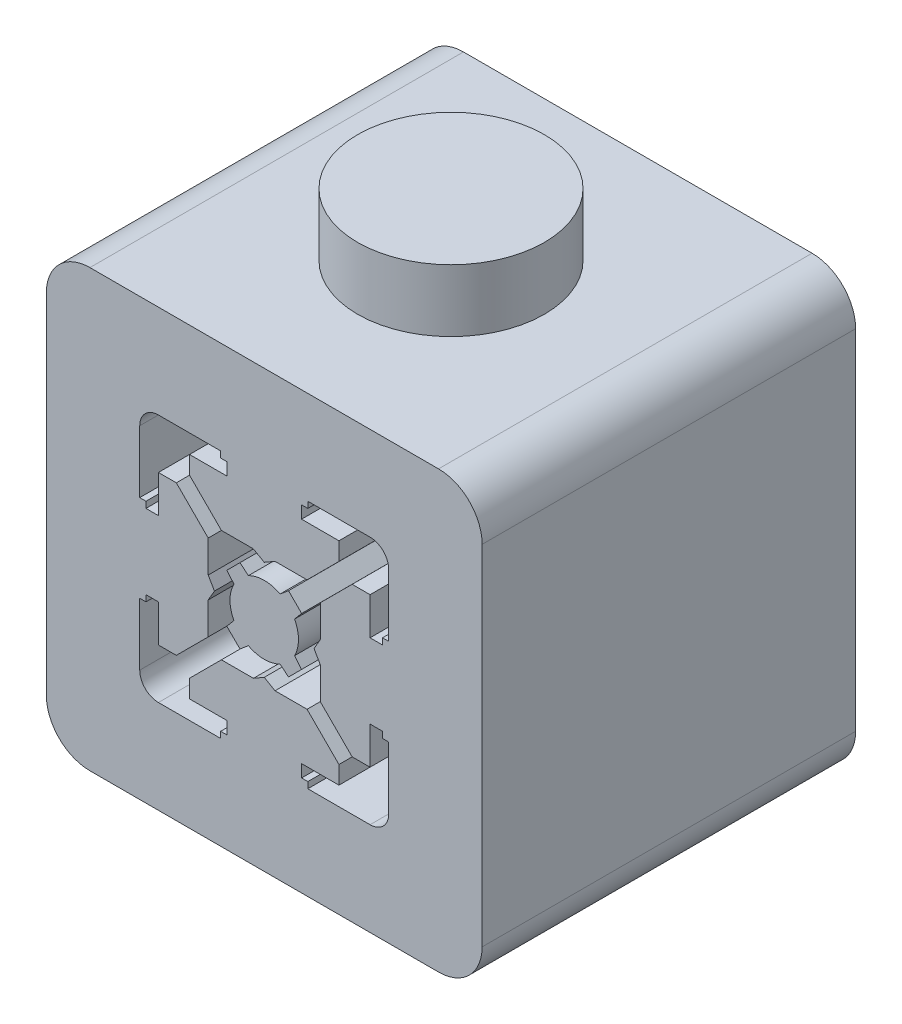
SolidWorks part; units mm, degrees
ref_plane "Plan de face" through (0, 0, 0) normal (0, 0, 1) x (1, 0, 0)
ref_plane "Plan de dessus" through (0, 0, 0) normal (0, 1, 0) x (1, 0, 0)
ref_plane "Plan de droite" through (0, 0, 0) normal (1, 0, 0) x (0, 0, -1)
sketch "Esquisse1" plane through (0, 0, 0) normal (0, 0, 1) x (1, 0, 0)
  line L0 (0, 0) -> (-4, 0) construction
  line L1 (-4, 0) -> (-4.5, 0.866)
  line L2 (-4, 0) -> (-4.5, -0.866)
  line L15 (-4.5, 0.866) -> (-4.5, 3.4393)
  line L16 (-4.5, 3.4393) -> (-7.0607, 6)
  line L17 (-7.0607, 6) -> (-8.5, 6)
  line L18 (-8.5, 6) -> (-8.5, 3)
  line L19 (-8.5, 3) -> (-9.5, 3)
  line L20 (-9.5, 3) -> (-9.5, 3.5)
  line L21 (-9.5, 3.5) -> (-10, 3.5)
  line L22 (-10, 3.5) -> (-10, 8.5)
  line L23 (0, 0) -> (0, 1.2745) construction
  line L24 (10, -3.5) -> (10, -8.5)
  line L25 (4.5, -3.4393) -> (7.0607, -6)
  line L26 (-9.5, -3.5) -> (-10, -3.5)
  line L27 (-9.5, -3) -> (-9.5, -3.5)
  line L28 (-8.5, -3) -> (-9.5, -3)
  line L29 (-8.5, -6) -> (-8.5, -3)
  line L30 (-7.0607, -6) -> (-8.5, -6)
  line L31 (-4.5, -0.866) -> (-4.5, -3.4393)
  line L32 (-4.5, -3.4393) -> (-7.0607, -6)
  line L33 (-10, -3.5) -> (-10, -8.5)
  line L34 (4.5, -0.866) -> (4.5, -3.4393)
  line L35 (7.0607, -6) -> (8.5, -6)
  line L36 (8.5, -6) -> (8.5, -3)
  line L37 (8.5, -3) -> (9.5, -3)
  line L38 (9.5, -3) -> (9.5, -3.5)
  line L39 (9.5, -3.5) -> (10, -3.5)
  line L40 (10, 3.5) -> (10, 8.5)
  line L41 (9.5, 3.5) -> (10, 3.5)
  line L42 (9.5, 3) -> (9.5, 3.5)
  line L43 (8.5, 3) -> (9.5, 3)
  line L44 (8.5, 6) -> (8.5, 3)
  line L45 (7.0607, 6) -> (8.5, 6)
  line L46 (4.5, 3.4393) -> (7.0607, 6)
  line L47 (4.5, 0.866) -> (4.5, 3.4393)
  line L48 (4, 0) -> (4.5, -0.866)
  line L49 (4, 0) -> (4.5, 0.866)
  line L50 (3.5, 10) -> (8.5, 10)
  line L51 (3.5, 9.5) -> (3.5, 10)
  line L52 (3, 8.5) -> (3, 9.5)
  line L53 (3, 9.5) -> (3.5, 9.5)
  line L54 (6, 8.5) -> (3, 8.5)
  line L55 (6, 7.0607) -> (6, 8.5)
  line L56 (3.4393, 4.5) -> (6, 7.0607)
  line L57 (0.866, 4.5) -> (3.4393, 4.5)
  line L58 (-0.866, 4.5) -> (-3.4393, 4.5)
  line L59 (-3.4393, 4.5) -> (-6, 7.0607)
  line L60 (-6, 7.0607) -> (-6, 8.5)
  line L61 (-6, 8.5) -> (-3, 8.5)
  line L62 (-3, 8.5) -> (-3, 9.5)
  line L63 (-3, 9.5) -> (-3.5, 9.5)
  line L64 (-3.5, 9.5) -> (-3.5, 10)
  line L65 (-3.5, 10) -> (-8.5, 10)
  line L66 (-14, 17.5) -> (14, 17.5)
  line L67 (9.5, -3.5) -> (10, -3.5)
  line L68 (8.5, -3) -> (9.5, -3)
  line L69 (9.5, -3) -> (9.5, -3.5)
  line L70 (8.5, -6) -> (8.5, -3)
  line L71 (7.0607, -6) -> (8.5, -6)
  line L72 (4.5, -3.4393) -> (7.0607, -6)
  line L73 (4.5, -0.866) -> (4.5, -3.4393)
  line L74 (4.5, 0.866) -> (4.5, 3.4393)
  line L75 (4.5, 3.4393) -> (7.0607, 6)
  line L76 (7.0607, 6) -> (8.5, 6)
  line L77 (8.5, 6) -> (8.5, 3)
  line L78 (8.5, 3) -> (9.5, 3)
  line L79 (9.5, 3) -> (9.5, 3.5)
  line L80 (9.5, 3.5) -> (10, 3.5)
  line L82 (-3.5, -10) -> (-8.5, -10)
  line L83 (-3.5, -9.5) -> (-3.5, -10)
  line L84 (-3, -8.5) -> (-3, -9.5)
  line L85 (-3, -9.5) -> (-3.5, -9.5)
  line L86 (-6, -8.5) -> (-3, -8.5)
  line L87 (-6, -7.0607) -> (-6, -8.5)
  line L88 (-3.4393, -4.5) -> (-6, -7.0607)
  line L89 (-0.866, -4.5) -> (-3.4393, -4.5)
  line L90 (0.866, -4.5) -> (3.4393, -4.5)
  line L91 (3.4393, -4.5) -> (6, -7.0607)
  line L92 (6, -7.0607) -> (6, -8.5)
  line L93 (6, -8.5) -> (3, -8.5)
  line L94 (3, -8.5) -> (3, -9.5)
  line L95 (3, -9.5) -> (3.5, -9.5)
  line L96 (3.5, -9.5) -> (3.5, -10)
  line L97 (3.5, -10) -> (8.5, -10)
  line L98 (0, 4) -> (0.866, 4.5)
  line L99 (0, 4) -> (-0.866, 4.5)
  line L100 (4, 0) -> (4.5, -0.866)
  line L101 (4, 0) -> (4.5, 0.866)
  line L102 (0, -4) -> (-0.866, -4.5)
  line L103 (0, -4) -> (0.866, -4.5)
  line L104 (0, 0) -> (-1.9002, -1.9879) construction
  line L105 (10, 3.5) -> (10, 10) [skipped]
  line L106 (10, -3.5) -> (10, -10) [skipped]
  line L108 (17.5, 14) -> (17.5, -14)
  line L109 (14, -17.5) -> (-14, -17.5)
  line L110 (-17.5, -14) -> (-17.5, 14)
  line L111 (1.9496, 3.0009) -> (1.2763, 2.4359)
  line L112 (-3.0009, 1.9496) -> (-2.4359, 1.2763)
  line L113 (-1.9473, 3.0032) -> (-1.2732, 2.4375)
  line L114 (-3.0009, 1.9496) -> (-1.9473, 3.0032)
  line L115 (1.9496, 3.0009) -> (3.0032, 1.9473)
  line L116 (3.0032, 1.9473) -> (2.4375, 1.2732)
  line L117 (3.0009, -1.9496) -> (2.4359, -1.2763)
  line L118 (3.0009, -1.9496) -> (1.9473, -3.0032)
  line L119 (1.9473, -3.0032) -> (1.2732, -2.4375)
  line L120 (-1.9496, -3.0009) -> (-1.2763, -2.4359)
  line L121 (-1.9496, -3.0009) -> (-3.0032, -1.9473)
  line L122 (-3.0032, -1.9473) -> (-2.4375, -1.2732)
  line L123 (0, 0) -> (-23.9117, 0) construction
  arc A0 (-10, 8.5) -> (-8.5, 10) centre (-8.5, 8.5) cw
  arc A1 (-10, -8.5) -> (-8.5, -10) centre (-8.5, -8.5) ccw
  arc A2 (10, -8.5) -> (8.5, -10) centre (8.5, -8.5) cw
  arc A3 (10, 8.5) -> (8.5, 10) centre (8.5, 8.5) ccw
  arc A4 (-2.4359, 1.2763) -> (-1.9002, -1.9879) centre (0, 0) ccw
  arc A5 (-14, 17.5) -> (-17.5, 14) centre (-14, 14) ccw
  arc A6 (17.5, 14) -> (14, 17.5) centre (14, 14) ccw
  arc A7 (14, -17.5) -> (17.5, -14) centre (14, -14) ccw
  arc A8 (-17.5, -14) -> (-14, -17.5) centre (-14, -14) ccw
  arc A9 (-2.4359, 1.2763) -> (-2.4375, -1.2732) centre (0, 0) ccw
  arc A10 (1.2763, 2.4359) -> (-1.2732, 2.4375) centre (0, 0) ccw
  arc A11 (2.4359, -1.2763) -> (2.4375, 1.2732) centre (0, 0) ccw
  arc A12 (-1.2763, -2.4359) -> (1.2732, -2.4375) centre (0, 0) ccw
  arc A13 (1.2763, 2.4359) -> (-1.2732, 2.4375) centre (0, 0) ccw
  arc A14 (2.4359, -1.2763) -> (2.4375, 1.2732) centre (0, 0) ccw
  arc A15 (-1.2763, -2.4359) -> (1.2732, -2.4375) centre (0, 0) ccw
  point P43 (-10, 10)
  point P98 (0, 0)
  point P101 (-10, -10)
  point P102 (10, -10)
  point P106 (0, 0)
  point P107 (10, 10)
  point P109 (-5.7803, 4.7197)
  point P116 (0, 17.5)
  point P130 (-27.239, 7.0465)
  point P135 (0, 0)
  point P146 (-24.7642, 4.5716)
  dimension "D15" = 1.5
  dimension "D16" = 1.5
  dimension "D14" = 1.5
  dimension "D17" = 5.5
  dimension "D23" = 7.5
  dimension "D2" = 120
  dimension "D3" = 1
  dimension "D5" = 20
  dimension "D6" = 6
  dimension "D7" = 12
  dimension "D8" = 135
  dimension "D9" = 5.5
  dimension "D10" = 4
  dimension "D11" = 0.5
  dimension "D12" = 4
  dimension "D13" = 0.5
  dimension "D18" = 4
  dimension "D19" = 4.5
  dimension "D20" = 28
  dimension "D21" = 4
  dimension "D4" = 1.5
  dimension "D22" = 4
extrude "Boss.-Extru.1" add sketch "Esquisse1" along normal blind 30 contours A1 L82 L83 L85 L84 L86 L87 L88 L89 L102 L103 L90 L91 L92 L93 L94 L95 L96 L97 A2 L24 L39 L38 L37 L36 L35 L25 L34 L48 L49 L47 L46 L45 L44 L43 L42 L41 L40 A3 L50 L51 L53 L52 L54 L55 L56 L57 L98 L99 L58 L59 L60 L61 L62 L63 L64 L65 A0 L22 L21 L20 L19 L18 L17 L16 L15 L1 L2 L31 L32 L30 L29 L28 L27 L26 L33 | L66 A6 L108 A7 L109 A8 L110 A5 | A4
extrude "Boss.-Extru.5" add sketch "Esquisse1<5>" along normal blind 30 separate body contours L120 A12 L119 L118 L117 A11 L116 L115 L111 A10 L113 L114 L112 A4 L122 L121 region at (0, 0, 0)
sketch "Esquisse1<5>" plane through (0, 0, 0) normal (0, 0, 1) x (1, 0, 0) same geometry as "Esquisse1"
sketch "Esquisse3" plane through (0, 17.5, 0) normal (0, 1, 0) x (1, 0, 0)
  line L0 (0, 0) -> (0, -30) construction
  line L1 (-14, -30) -> (14, -30) construction
  line L2 (-14, -15) -> (14, -15) construction
  line L3 (-14, -30) -> (-14, 0) construction
  line L4 (14, -30) -> (14, 0) construction
  circle A0 centre (0, -15) radius 7.5
  dimension "D1" = 15
extrude "Boss.-Extru.2" add sketch "Esquisse3" along normal blind 5
ref_plane "Plan2" through (0, 0, 15) normal (0, 0, 1) x (1, 0, 0)
sketch "Esquisse14" plane through (0, 0, 15) normal (0, 0, 1) x (1, 0, 0)
  line L0 (0, 0) -> (-4, 0) construction
  line L1 (-4, 0) -> (-4.5, 0.866)
  line L2 (-4, 0) -> (-4.5, -0.866)
  line L15 (-4.5, 0.866) -> (-4.5, 3.4393)
  line L16 (-4.5, 3.4393) -> (-7.0607, 6)
  line L17 (-7.0607, 6) -> (-8.5, 6)
  line L18 (-8.5, 6) -> (-8.5, 3)
  line L19 (-8.5, 3) -> (-9.5, 3)
  line L20 (-9.5, 3) -> (-9.5, 3.5)
  line L21 (-9.5, 3.5) -> (-10, 3.5)
  line L22 (-10, 3.5) -> (-10, 8.5)
  line L23 (0, 0) -> (0, 1.2745) construction
  line L24 (10, -3.5) -> (10, -8.5)
  line L25 (4.5, -3.4393) -> (7.0607, -6)
  line L26 (-9.5, -3.5) -> (-10, -3.5)
  line L27 (-9.5, -3) -> (-9.5, -3.5)
  line L28 (-8.5, -3) -> (-9.5, -3)
  line L29 (-8.5, -6) -> (-8.5, -3)
  line L30 (-7.0607, -6) -> (-8.5, -6)
  line L31 (-4.5, -0.866) -> (-4.5, -3.4393)
  line L32 (-4.5, -3.4393) -> (-7.0607, -6)
  line L33 (-10, -3.5) -> (-10, -8.5)
  line L34 (4.5, -0.866) -> (4.5, -3.4393)
  line L35 (7.0607, -6) -> (8.5, -6)
  line L36 (8.5, -6) -> (8.5, -3)
  line L37 (8.5, -3) -> (9.5, -3)
  line L38 (9.5, -3) -> (9.5, -3.5)
  line L39 (9.5, -3.5) -> (10, -3.5)
  line L40 (10, 3.5) -> (10, 8.5)
  line L41 (9.5, 3.5) -> (10, 3.5)
  line L42 (9.5, 3) -> (9.5, 3.5)
  line L43 (8.5, 3) -> (9.5, 3)
  line L44 (8.5, 6) -> (8.5, 3)
  line L45 (7.0607, 6) -> (8.5, 6)
  line L46 (4.5, 3.4393) -> (7.0607, 6)
  line L47 (4.5, 0.866) -> (4.5, 3.4393)
  line L48 (4, 0) -> (4.5, -0.866)
  line L49 (4, 0) -> (4.5, 0.866)
  line L50 (3.5, 10) -> (8.5, 10)
  line L51 (3.5, 9.5) -> (3.5, 10)
  line L52 (3, 8.5) -> (3, 9.5)
  line L53 (3, 9.5) -> (3.5, 9.5)
  line L54 (6, 8.5) -> (3, 8.5)
  line L55 (6, 7.0607) -> (6, 8.5)
  line L56 (3.4393, 4.5) -> (6, 7.0607)
  line L57 (0.866, 4.5) -> (3.4393, 4.5)
  line L58 (-0.866, 4.5) -> (-3.4393, 4.5)
  line L59 (-3.4393, 4.5) -> (-6, 7.0607)
  line L60 (-6, 7.0607) -> (-6, 8.5)
  line L61 (-6, 8.5) -> (-3, 8.5)
  line L62 (-3, 8.5) -> (-3, 9.5)
  line L63 (-3, 9.5) -> (-3.5, 9.5)
  line L64 (-3.5, 9.5) -> (-3.5, 10)
  line L65 (-3.5, 10) -> (-8.5, 10)
  line L67 (9.5, -3.5) -> (10, -3.5)
  line L68 (8.5, -3) -> (9.5, -3)
  line L69 (9.5, -3) -> (9.5, -3.5)
  line L70 (8.5, -6) -> (8.5, -3)
  line L71 (7.0607, -6) -> (8.5, -6)
  line L72 (4.5, -3.4393) -> (7.0607, -6)
  line L73 (4.5, -0.866) -> (4.5, -3.4393)
  line L74 (4.5, 0.866) -> (4.5, 3.4393)
  line L75 (4.5, 3.4393) -> (7.0607, 6)
  line L76 (7.0607, 6) -> (8.5, 6)
  line L77 (8.5, 6) -> (8.5, 3)
  line L78 (8.5, 3) -> (9.5, 3)
  line L79 (9.5, 3) -> (9.5, 3.5)
  line L80 (9.5, 3.5) -> (10, 3.5)
  line L82 (-3.5, -10) -> (-8.5, -10)
  line L83 (-3.5, -9.5) -> (-3.5, -10)
  line L84 (-3, -8.5) -> (-3, -9.5)
  line L85 (-3, -9.5) -> (-3.5, -9.5)
  line L86 (-6, -8.5) -> (-3, -8.5)
  line L87 (-6, -7.0607) -> (-6, -8.5)
  line L88 (-3.4393, -4.5) -> (-6, -7.0607)
  line L89 (-0.866, -4.5) -> (-3.4393, -4.5)
  line L90 (0.866, -4.5) -> (3.4393, -4.5)
  line L91 (3.4393, -4.5) -> (6, -7.0607)
  line L92 (6, -7.0607) -> (6, -8.5)
  line L93 (6, -8.5) -> (3, -8.5)
  line L94 (3, -8.5) -> (3, -9.5)
  line L95 (3, -9.5) -> (3.5, -9.5)
  line L96 (3.5, -9.5) -> (3.5, -10)
  line L97 (3.5, -10) -> (8.5, -10)
  line L98 (0, 4) -> (0.866, 4.5)
  line L99 (0, 4) -> (-0.866, 4.5)
  line L100 (4, 0) -> (4.5, -0.866)
  line L101 (4, 0) -> (4.5, 0.866)
  line L102 (0, -4) -> (-0.866, -4.5)
  line L103 (0, -4) -> (0.866, -4.5)
  line L104 (0, 0) -> (-1.9445, 1.9445) construction
  line L105 (10, 3.5) -> (10, 10)
  line L106 (10, -3.5) -> (10, -10)
  arc A0 (-10, 8.5) -> (-8.5, 10) centre (-8.5, 8.5) cw
  arc A1 (-10, -8.5) -> (-8.5, -10) centre (-8.5, -8.5) ccw
  arc A2 (10, -8.5) -> (8.5, -10) centre (8.5, -8.5) cw
  arc A3 (10, 8.5) -> (8.5, 10) centre (8.5, 8.5) ccw
  circle A4 centre (0, 0) radius 2.75
  point P43 (-10, 10)
  point P98 (0, 0)
  point P101 (-10, -10)
  point P102 (10, -10)
  point P106 (0, 0)
  point P107 (10, 10)
  point P109 (-5.7803, 4.7197)
  dimension "D15" = 1.5
  dimension "D16" = 1.5
  dimension "D14" = 1.5
  dimension "D17" = 5.5
  dimension "D2" = 120
  dimension "D3" = 1
  dimension "D5" = 20
  dimension "D6" = 6
  dimension "D7" = 12
  dimension "D8" = 135
  dimension "D9" = 5.5
  dimension "D10" = 4
  dimension "D11" = 0.5
  dimension "D12" = 4
  dimension "D13" = 0.5
  dimension "D18" = 4
  dimension "D19" = 4.5
  dimension "D4" = 1.5
extrude "Boss.-Extru.8" add sketch "Esquisse14" along normal blind 5 and the other way blind 5 contours A1 L82 L83 L85 L84 L86 L87 L88 L89 L102 L103 L90 L91 L92 L93 L94 L95 L96 L97 A2 L24 L39 L38 L37 L36 L35 L25 L34 L48 L49 L47 L46 L45 L44 L43 L42 L41 L40 A3 L50 L51 L53 L52 L54 L55 L56 L57 L98 L99 L58 L59 L60 L61 L62 L63 L64 L65 A0 L22 L21 L20 L19 L18 L17 L16 L15 L1 L2 L31 L32 L30 L29 L28 L27 L26 L33
